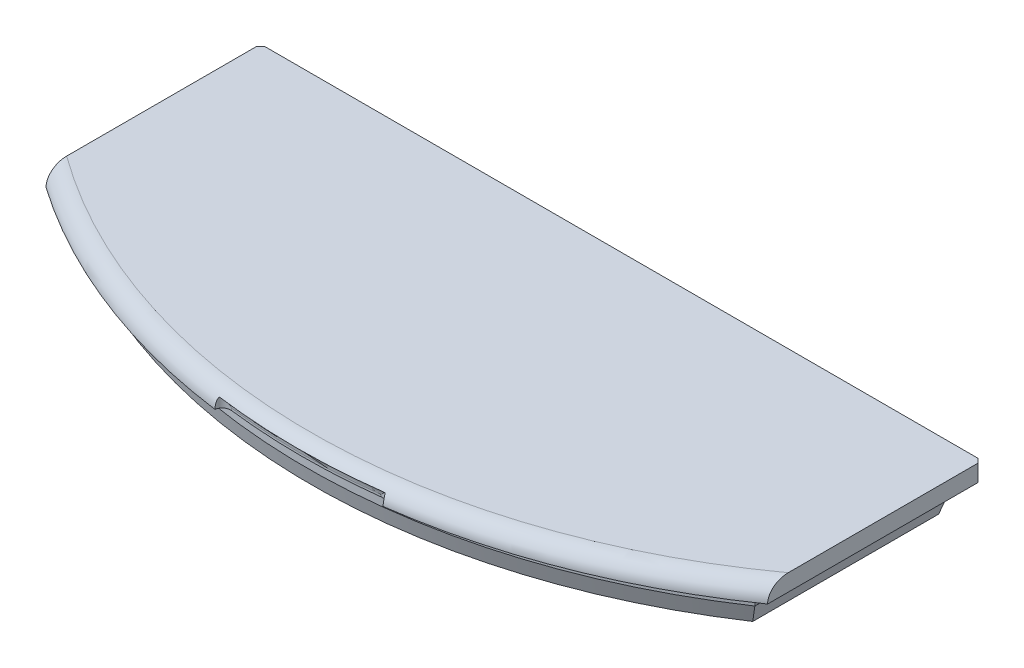
SolidWorks part; units mm, degrees
ref_plane "정면" through (0, 0, 0) normal (0, 0, 1) x (1, 0, 0)
ref_plane "윗면" through (0, 0, 0) normal (0, 1, 0) x (1, 0, 0)
ref_plane "우측면" through (0, 0, 0) normal (1, 0, 0) x (0, 0, -1)
sketch "스케치1" plane through (0, 0, 0) normal (0, 1, 0) x (1, 0, 0)
  line L0 (0, -173.7607) -> (0, -125.3808) construction
  line L1 (-51.4079, 0) -> (-23.4688, 0) construction
  line L2 (85.8, -72) -> (85.8, -123.038)
  line L3 (85.8, -72) -> (-85.8, -72)
  line L5 (85.8, -73) -> (85.8, -123.038) construction
  line L6 (-85.8, -72) -> (-85.8, -123.038)
  arc A0 (-85.8, -123.038) -> (85.8, -123.038) centre (0, 0) ccw
  arc A2 (-85.8, -119.3623) -> (85.8, -119.3623) centre (0, 0) ccw construction
  point P14 (0, -72)
  dimension "D1" = 300
  dimension "D3" = 72
extrude "보스-돌출1" add sketch "스케치1" along normal blind 4
chamfer "모따기1" distance 1 angle 45 2 edges at (-85.8, 2, 72) (85.8, 2, 72)
sketch "스케치2" plane through (0, 0, 0) normal (0, -1, 0) x (1, 0, 0)
  line L0 (0, 54.7151) -> (0, 13.0129) construction
  line L1 (-49.583, 0) -> (72.957, 0) construction
  line L2 (-81.7, 76.1) -> (-81.7, 121.9645)
  line L3 (-77.8, 80) -> (-77.8, 119.7456)
  line L4 (81.7, 76.1) -> (-81.7, 76.1)
  line L5 (84.8, 72) -> (-84.8, 72) construction
  line L6 (-85.8, 73) -> (-85.8, 123.038) construction
  line L7 (-77.8, 80) -> (77.8, 80)
  line L8 (77.8, 80) -> (77.8, 119.7456)
  line L9 (81.7, 76.1) -> (81.7, 121.9645)
  arc A2 (77.8, 119.7456) -> (-77.8, 119.7456) centre (0, 0) ccw
  arc A3 (81.7, 121.9645) -> (-81.7, 121.9645) centre (0, 0) ccw
  point P19 (0, 80)
  point P20 (0, 76.1)
  dimension "D1" = 146.8
  dimension "D2" = 142.8
  dimension "D3" = 4.1
  dimension "D4" = 4.1
  dimension "D5" = 3.9
  dimension "D6" = 3.9
extrude "보스-돌출2" add sketch "스케치2" along normal blind 7
chamfer "모따기2" distance 4 angle 15 4 edges at (81.7, -7, 99.0323) (0, -7, 146.8) (-81.7, -7, 99.0323) (0, -7, 76.1) first distance on face at (81.7, -3.5, 99.0323) first distance on face at (0, -3.5, 134.3823) first distance on face at (-81.7, -3.5, 99.0323) first distance on face at (0, -3.5, 76.1)
sketch "스케치3" plane through (0, 0, 0) normal (0, -1, 0) x (1, 0, 0)
  line L0 (0, 41.8819) -> (0, -44.2394) construction
  line L1 (20, 146.6424) -> (20, 148.6607)
  line L2 (-20, 146.6424) -> (-20, 148.6607)
  arc A0 (85.8, 123.038) -> (-85.8, 123.038) centre (0, 0) ccw construction
  arc A1 (20, 148.6607) -> (-20, 148.6607) centre (0, 0) ccw
  arc A2 (20, 146.6424) -> (-20, 146.6424) centre (0, 0) ccw
  arc A3 (85.8, 123.038) -> (-85.8, 123.038) centre (0, 0) ccw construction
  arc A4 (84.656, 121.3975) -> (-84.656, 121.3975) centre (0, 0) ccw construction
  dimension "D2" = 20
  dimension "D1" = 2
extrude "컷-돌출1" cut sketch "스케치3" against normal blind 2.5
fillet "필렛1" radius 2 3 edges at (20, 1.25, 146.6424) (-20, 1.25, 146.6424) (0, 2.5, 148)
fillet "필렛2" radius 4 1 edges at (0, 4, 150)
